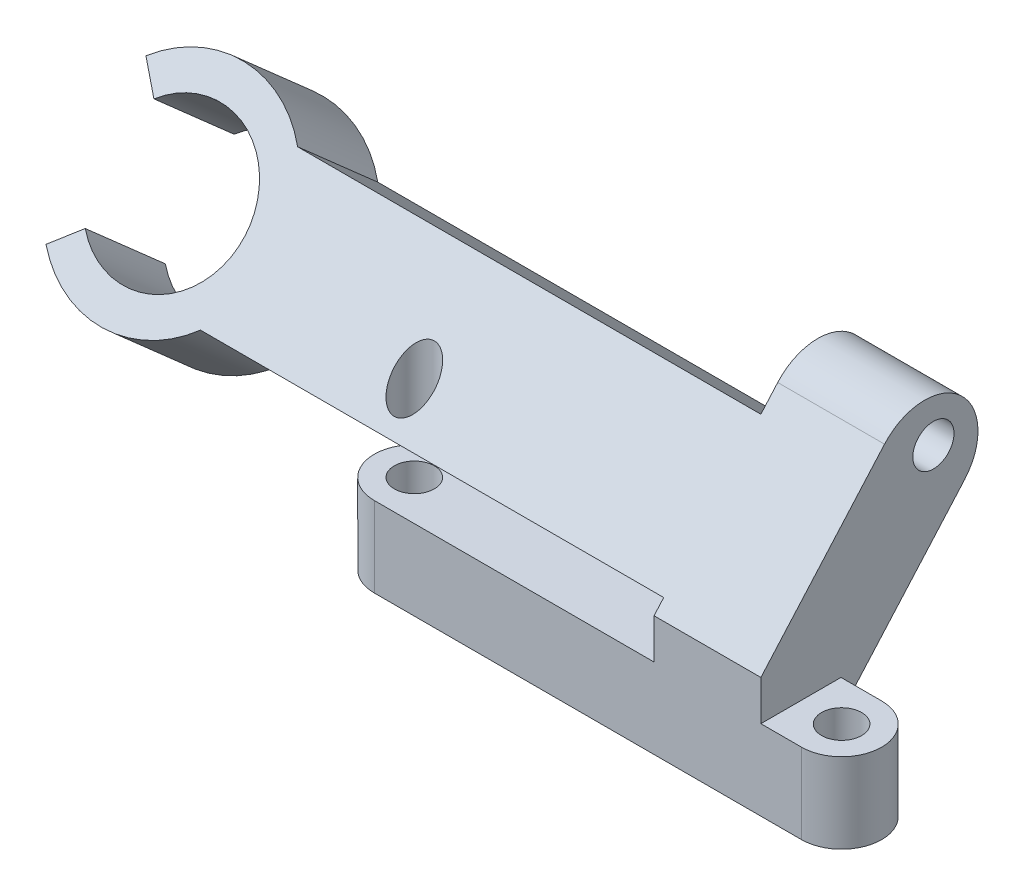
SolidWorks part; units mm, degrees
ref_plane "前基準面" through (0, 0, 0) normal (0, 0, 1) x (1, 0, 0)
ref_plane "上基準面" through (0, 0, 0) normal (0, 1, 0) x (1, 0, 0)
ref_plane "右基準面" through (0, 0, 0) normal (1, 0, 0) x (0, 0, -1)
sketch "草圖1" plane through (0, 0, 0) normal (0, 1, 0) x (1, 0, 0)
  line L0 (-38.677, 0) -> (-6.677, 0) construction
  line L1 (-38.677, 3) -> (-6.677, 3)
  line L2 (-38.677, -3) -> (-6.677, -3)
  line L4 (-17.7228, 3) -> (-9.7228, 3)
  line L5 (-17.7228, 3) -> (-17.7228, -3)
  line L6 (-17.7228, -3) -> (-9.7228, -3)
  line L7 (-9.7228, 3) -> (-9.7228, -3)
  arc A0 (-38.677, 3) -> (-38.677, -3) centre (-38.677, 0) ccw
  arc A1 (-6.677, -3) -> (-6.677, 3) centre (-6.677, 0) ccw
  circle A2 centre (-6.677, 0) radius 1.5
  circle A3 centre (-38.677, 0) radius 1.5
  point P3 (-22.677, 0)
  dimension "D1" = 32
  dimension "D2" = 8
  dimension "D4" = 3
  dimension "D3" = 6
extrude "填料-伸長2" add sketch "草圖1" against normal blind 6 contours A3 L5 L1 A0 L2 | L5 L0 L7 L1 | L0 L5 L2 L7 | L2 A1 L1 L7 A2 region at (-17.9697, 0, 1.5) region at (-13.7228, 0, -1.5) region at (-13.7228, 0, 1.5) region at (-9.6376, 0, -1.5)
extrude "填料-伸長3" add sketch "草圖1<4>" along normal blind 3 contours L0 L5 L2 L7 | L5 L0 L7 L1 region at (-13.7228, 0, -1.5) region at (-13.7228, 0, 1.5)
sketch "草圖1<4>" plane through (0, 0, 0) normal (0, 1, 0) x (1, 0, 0) same geometry as "草圖1"
sketch "草圖3" plane through (-9.7228, 0, 0) normal (1, 0, 0) x (0, 0, -1)
  line L0 (-3, 3) -> (-3, 0) construction
  line L2 (-3, 2.6558) -> (-3, 0)
  line L3 (9.2601, 10.8542) -> (0, 0.3542) construction
  line L4 (3, -6) -> (3, 0) construction
  line L5 (12.2601, 8.2085) -> (6.2601, 13.5)
  line L6 (12.2601, 8.2085) -> (3, -2.2915)
  line L7 (6.2601, 13.5) -> (-3, 3)
  line L8 (3, -2.2915) -> (-3, 3)
  line L9 (12.2601, 8.2085) -> (3, -2.2915)
  line L10 (6.2601, 13.5) -> (-3, 3)
  arc A0 (12.2601, 8.2085) -> (6.2601, 13.5) centre (9.2601, 10.8542) ccw
  arc A1 (-3, 3) -> (3, -2.2915) centre (0, 0.3542) ccw
  point P15 (4.6301, 5.6042)
  dimension "D1" = 8
  dimension "D2" = 14
extrude "填料-伸長28" add sketch "草圖3" against normal blind 8 contours L5 A0 | L5 L7 L8 L6 region at (-9.7228, 12.1275, -10.383)
sketch "草圖8" plane through (-9.7228, 0, 0) normal (1, 0, 0) x (0, 0, -1)
  line L0 (6.2601, 13.5) -> (-3, 3) construction
  circle A0 centre (9.9216, 11.6042) radius 1.5424
  arc A1 (12.2601, 8.2085) -> (6.2601, 13.5) centre (9.2601, 10.8542) ccw construction
  point P4 (11.9059, 13.8542)
  dimension "D3" = 3.0847
  dimension "D1" = 4
  dimension "D2" = 3
extrude "除料-伸長2" cut sketch "草圖8" against normal blind 12 contours A0
sketch "草圖9" plane through (-17.7228, 0, 0) normal (-1, 0, 0) x (0, 0, 1)
  line L0 (-10.9991, 6.7787) -> (-4.9991, 12.0702)
  line L1 (-10.9991, 6.7787) -> (-3.7233, -1.4713)
  line L2 (-4.9991, 12.0702) -> (2.2767, 3.8202)
  line L3 (-3.7233, -1.4713) -> (2.2767, 3.8202)
  line L4 (-12.2601, 8.2085) -> (-3, -2.2915) construction
  line L5 (-6.2601, 13.5) -> (3, 3) construction
  dimension "D1" = 11
extrude "填料-伸長29" add sketch "草圖9" along normal blind 35
sketch "草圖10" plane through (0, -2.4908, -2.8243) normal (0, -0.6614, -0.75) x (-1, 0, 0)
  line L0 (52.7228, 6.8592) -> (58.2228, 6.8592) construction
  line L1 (52.7228, 12.3592) -> (52.7228, 1.3592) construction
  line L2 (58.2228, 6.8592) -> (63.8796, 12.5161)
  line L3 (58.2228, 6.8592) -> (63.8796, 1.2024)
  arc A0 (62.1118, 10.7483) -> (62.1118, 2.9701) centre (58.2228, 6.8592) ccw
  arc A1 (63.8796, 12.5161) -> (63.8796, 1.2024) centre (58.2228, 6.8592) ccw
  line M9 (17.7228, 1.3592) -> (52.7228, 1.3592)
  line M10 (52.7228, 1.3592) -> (52.7228, 12.3592)
  line M11 (52.7228, 12.3592) -> (17.7228, 12.3592)
  dimension "D1" = 11
  dimension "D2" = 16
  dimension "D3" = 45
  dimension "D4" = 45
extrude "填料-伸長30" add sketch "草圖10" against normal blind 8 contours L2 A1 A0 M11 M10 | A1 L3 A0 M9 M10 | A1 M11 M9 M10 region at (-57.6726, 7.05, -11.2385) region at (-57.6726, -1.7427, -3.484) region at (-51.7036, 2.6537, -7.3612)
sketch "草圖11" plane through (0, -6, 0) normal (0, -1, 0) x (1, 0, 0)
  circle A0 centre (-38.677, 0) radius 1.5
extrude "除料-伸長3" cut sketch "草圖11" against normal blind 20
